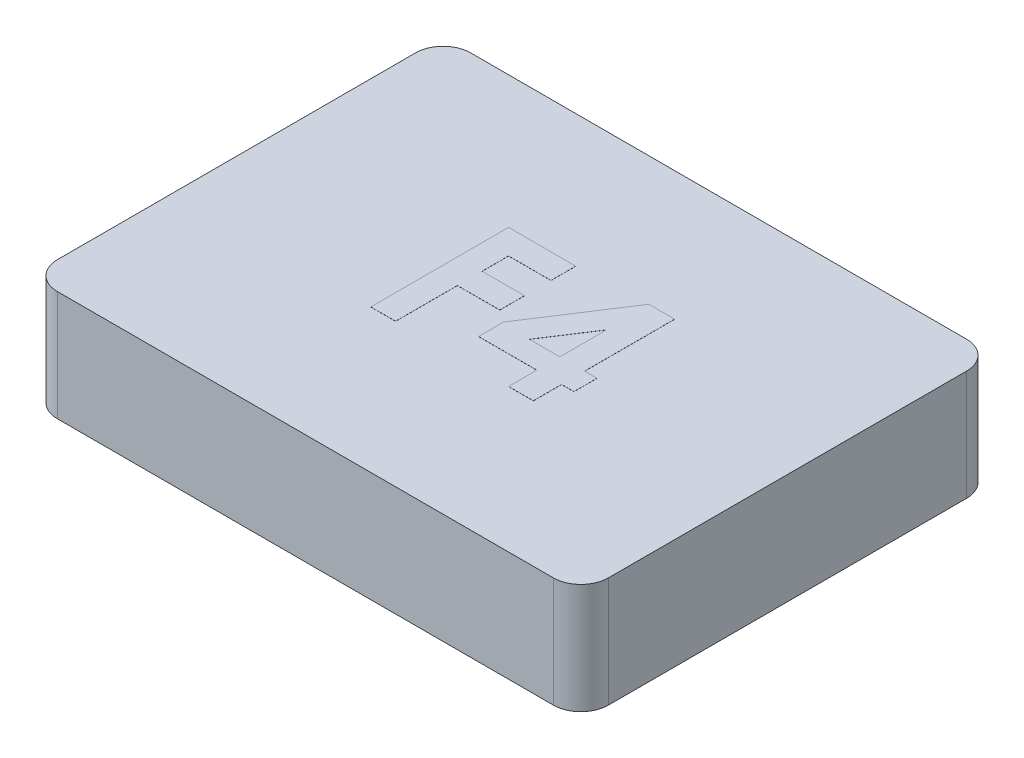
SolidWorks part; units mm, degrees
ref_plane "Front Plane" through (0, 0, 0) normal (0, 0, 1) x (1, 0, 0)
ref_plane "Top Plane" through (0, 0, 0) normal (0, 1, 0) x (1, 0, 0)
ref_plane "Right Plane" through (0, 0, 0) normal (1, 0, 0) x (0, 0, -1)
sketch "Sketch1" plane through (0, 0, 0) normal (0, 1, 0) x (1, 0, 0)
  line L0 (0, 0) -> (12.7, 0)
  line L1 (12.7, 0) -> (12.7, 9.525)
  line L2 (12.7, 9.525) -> (0, 9.525)
  line L3 (0, 9.525) -> (0, 0)
  dimension "D1" = 12.7
  dimension "D2" = 9.525
extrude "Boss-Extrude1" add sketch "Sketch1" along normal blind 2.54
fillet "Fillet1" radius 0.635 4 edges at (0, 1.27, -9.525) (12.7, 1.27, -9.525) (12.7, 1.27, 0) (0, 1.27, 0)
shell "Shell1" thickness 0.635 removed face at (6.35, 0, -4.7625)
sketch "Sketch2" plane through (0, 1.905, 0) normal (0, -1, 0) x (-1, 0, 0)
  line L0 (-0.635, 4.7625) -> (-12.065, 4.7625) construction
  line L1 (-0.635, 8.89) -> (-0.635, 0.635) construction
  line L2 (-12.065, 0.635) -> (-12.065, 8.89) construction
  line L3 (-6.35, 0.635) -> (-6.35, 8.89) construction
  line L4 (-0.635, 0.635) -> (-12.065, 0.635) construction
  line L5 (-12.065, 8.89) -> (-0.635, 8.89) construction
  circle A0 centre (-6.35, 4.7625) radius 2.54
  dimension "D1" = 5.08
extrude "Boss-Extrude2" add sketch "Sketch2" along normal up to surface (1.905 mm away) up to face at (6.35, 0, -4.7625)
sketch "Sketch3" plane through (0, 2.54, 0) normal (0, 1, 0) x (1, 0, 0)
  line L0 (0.635, 0) -> (12.065, 0) construction
  line L1 (0, 8.89) -> (0, 0.635) construction
  text T0 "<b>F4</b>"
  dimension "D1" = 3.302
  dimension "D2" = 4.191
extrude "Boss-Extrude3" add sketch "Sketch3" along normal blind 0.0025
